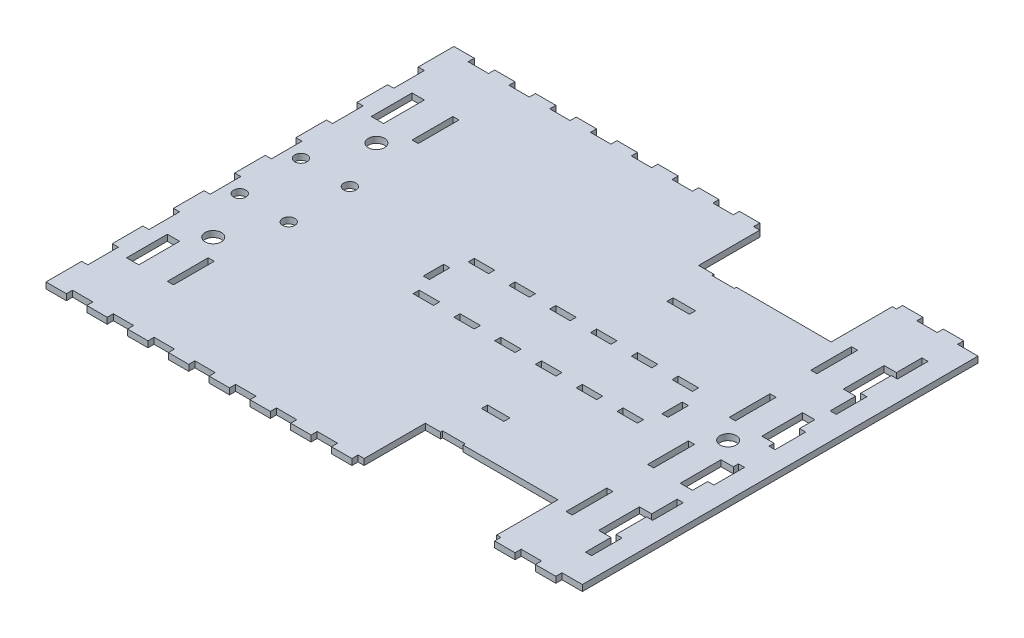
SolidWorks part; units mm, degrees
ref_plane "Front Plane" through (0, 0, 0) normal (0, 0, 1) x (1, 0, 0)
ref_plane "Top Plane" through (0, 0, 0) normal (0, 1, 0) x (1, 0, 0)
ref_plane "Right Plane" through (0, 0, 0) normal (1, 0, 0) x (0, 0, -1)
sketch "Sketch3" plane through (0, 0, 0) normal (0, 1, 0) x (1, 0, 0)
  line L0 (0, 0) -> (-300, 0) construction
  line L1 (-300, -97) -> (-300, 97)
  line L2 (-290, 100) -> (-300, 100)
  line L3 (-290, 97) -> (-290, 100)
  line L4 (-280, 97) -> (-290, 97)
  line L5 (-300, 100) -> (-300, 97)
  line L6 (-270, 100) -> (-280, 100)
  line L7 (-270, 97) -> (-270, 100)
  line L8 (-260, 97) -> (-270, 97)
  line L9 (-280, 100) -> (-280, 97)
  line L10 (-250, 100) -> (-260, 100)
  line L11 (-250, 97) -> (-250, 100)
  line L12 (-240, 97) -> (-250, 97)
  line L13 (-260, 100) -> (-260, 97)
  line L14 (-150, -100) -> (-150, 100) construction
  line L15 (-230, 100) -> (-240, 100)
  line L16 (-230, 97) -> (-230, 100)
  line L17 (-220, 97) -> (-230, 97)
  line L18 (-240, 100) -> (-240, 97)
  line L19 (-210, 100) -> (-220, 100)
  line L20 (-210, 97) -> (-210, 100)
  line L21 (-200, 97) -> (-210, 97)
  line L22 (-40, 97) -> (-40, -97)
  line L23 (-50, 37.5) -> (-53, 37.5)
  line L24 (-50, 7.5) -> (-53, 7.5)
  line L25 (-50, -45.947) -> (-50, 45.947) construction
  line L26 (-247, 37.5) -> (-250, 37.5) construction
  line L27 (-247, 7.5) -> (-250, 7.5) construction
  line L28 (-247, 48.5) -> (-247, -48.5) construction
  line L29 (-247, 48.5) -> (-223, 48.5) construction
  line L30 (-223, 48.5) -> (-223, -48.5) construction
  line L31 (-210, 15) -> (-90, 15) construction
  line L32 (-90, 15) -> (-90, 5) construction
  line L33 (-50, 7.5) -> (-50, 22.5)
  line L34 (-220, 100) -> (-220, 97)
  line L35 (-190, 100) -> (-200, 100)
  line L36 (-190, 97) -> (-190, 100)
  line L37 (-180, 97) -> (-190, 97)
  line L38 (-200, 100) -> (-200, 97)
  line L39 (-170, 100) -> (-180, 100)
  line L40 (-170, 97) -> (-170, 100)
  line L41 (-160, 97) -> (-170, 97)
  line L42 (-180, 100) -> (-180, 97)
  line L43 (-150, 100) -> (-160, 100)
  line L44 (-150, 97) -> (-150, 100)
  line L45 (-140, 97) -> (-150, 97)
  line L46 (-160, 100) -> (-160, 97)
  line L47 (-130, 100) -> (-140, 100)
  line L48 (-130, 97) -> (-130, 100)
  line L49 (-120, 97) -> (-130, 97)
  line L50 (-140, 100) -> (-140, 97)
  line L51 (-110, 100) -> (-120, 100)
  line L52 (-110, 97) -> (-110, 100)
  line L53 (-100, 97) -> (-110, 97)
  line L54 (-120, 100) -> (-120, 97)
  line L55 (-90, 100) -> (-100, 100)
  line L56 (-90, 97) -> (-90, 100)
  line L57 (-80, 97) -> (-90, 97)
  line L58 (-100, 100) -> (-100, 97)
  line L59 (-70, 100) -> (-80, 100)
  line L60 (-70, 97) -> (-70, 100)
  line L61 (-60, 97) -> (-70, 97)
  line L62 (-80, 100) -> (-80, 97)
  line L63 (-50, 100) -> (-60, 100)
  line L64 (-50, 97) -> (-50, 100)
  line L65 (-40, 97) -> (-50, 97)
  line L66 (-60, 100) -> (-60, 97)
  line L67 (-50, 22.5) -> (-53, 22.5)
  line L68 (-210, -15) -> (-90, -15) construction
  line L69 (-53, 7.5) -> (-53, 22.5)
  line L70 (-50, 37.5) -> (-50, 52.5)
  line L71 (-50, 52.5) -> (-53, 52.5)
  line L72 (-53, 37.5) -> (-53, 52.5)
  line L73 (-50, 67.5) -> (-53, 67.5)
  line L74 (-50, 67.5) -> (-50, 82.5)
  line L75 (-50, 82.5) -> (-53, 82.5)
  line L76 (-60, -100) -> (-60, -97)
  line L77 (-40, -97) -> (-50, -97)
  line L78 (-50, -97) -> (-50, -100)
  line L79 (-50, -100) -> (-60, -100)
  line L80 (-80, -100) -> (-80, -97)
  line L81 (-60, -97) -> (-70, -97)
  line L82 (-70, -97) -> (-70, -100)
  line L83 (-70, -100) -> (-80, -100)
  line L84 (-100, -100) -> (-100, -97)
  line L85 (-80, -97) -> (-90, -97)
  line L86 (-90, -97) -> (-90, -100)
  line L87 (-90, -100) -> (-100, -100)
  line L88 (-120, -100) -> (-120, -97)
  line L89 (-100, -97) -> (-110, -97)
  line L90 (-110, -97) -> (-110, -100)
  line L91 (-110, -100) -> (-120, -100)
  line L92 (-140, -100) -> (-140, -97)
  line L93 (-120, -97) -> (-130, -97)
  line L94 (-130, -97) -> (-130, -100)
  line L95 (-130, -100) -> (-140, -100)
  line L96 (-160, -100) -> (-160, -97)
  line L97 (-140, -97) -> (-150, -97)
  line L98 (-150, -97) -> (-150, -100)
  line L99 (-150, -100) -> (-160, -100)
  line L100 (-180, -100) -> (-180, -97)
  line L101 (-160, -97) -> (-170, -97)
  line L102 (-170, -97) -> (-170, -100)
  line L103 (-170, -100) -> (-180, -100)
  line L104 (-200, -100) -> (-200, -97)
  line L105 (-180, -97) -> (-190, -97)
  line L106 (-190, -97) -> (-190, -100)
  line L107 (-190, -100) -> (-200, -100)
  line L108 (-247, -48.5) -> (-223, -48.5) construction
  line L109 (-247, 7.5) -> (-247, 22.5) construction
  line L110 (-220, -100) -> (-220, -97)
  line L111 (-53, 67.5) -> (-53, 82.5)
  line L112 (-53, -67.5) -> (-53, -82.5)
  line L113 (-50, -82.5) -> (-53, -82.5)
  line L114 (-200, -97) -> (-210, -97)
  line L115 (-210, -97) -> (-210, -100)
  line L116 (-210, -100) -> (-220, -100)
  line L117 (-240, -100) -> (-240, -97)
  line L118 (-220, -97) -> (-230, -97)
  line L119 (-230, -97) -> (-230, -100)
  line L120 (-230, -100) -> (-240, -100)
  line L121 (-50, -67.5) -> (-50, -82.5)
  line L122 (-260, -100) -> (-260, -97)
  line L123 (-240, -97) -> (-250, -97)
  line L124 (-250, -97) -> (-250, -100)
  line L125 (-250, -100) -> (-260, -100)
  line L126 (-280, -100) -> (-280, -97)
  line L127 (-260, -97) -> (-270, -97)
  line L128 (-270, -97) -> (-270, -100)
  line L129 (-270, -100) -> (-280, -100)
  line L130 (-300, -100) -> (-300, -97)
  line L131 (-210, 15) -> (-210, -15) construction
  line L132 (-115, 15) -> (-125, 15)
  line L133 (-90, 5) -> (-93, 5)
  line L134 (-90, 5) -> (-90, -5)
  line L135 (-90, -5) -> (-93, -5)
  line L136 (-93, 5) -> (-93, -5)
  line L137 (-95, 15) -> (-105, 15)
  line L138 (-95, 15) -> (-95, 12)
  line L139 (-95, 12) -> (-105, 12)
  line L140 (-105, 15) -> (-105, 12)
  line L141 (-115, 12) -> (-125, 12)
  line L142 (-125, 15) -> (-125, 12)
  line L143 (-135, 15) -> (-145, 15)
  line L144 (-135, 12) -> (-145, 12)
  line L145 (-145, 15) -> (-145, 12)
  line L146 (-155, 15) -> (-165, 15)
  line L147 (-155, 12) -> (-165, 12)
  line L148 (-165, 15) -> (-165, 12)
  line L149 (-175, 15) -> (-185, 15)
  line L150 (-175, 12) -> (-185, 12)
  line L151 (-185, 15) -> (-185, 12)
  line L152 (-195, 15) -> (-205, 15)
  line L153 (-195, 12) -> (-205, 12)
  line L154 (-205, 15) -> (-205, 12)
  line L155 (-195, 12) -> (-195, 15)
  line L156 (-175, 12) -> (-175, 15)
  line L157 (-155, 12) -> (-155, 15)
  line L158 (-135, 12) -> (-135, 15)
  line L159 (-115, 12) -> (-115, 15)
  line L160 (-207, 5) -> (-207, -5)
  line L161 (-210, -5) -> (-207, -5)
  line L162 (-210, 5) -> (-210, -5)
  line L163 (-210, 5) -> (-207, 5)
  line L164 (-115, -12) -> (-115, -15)
  line L165 (-135, -12) -> (-135, -15)
  line L166 (-155, -12) -> (-155, -15)
  line L167 (-175, -12) -> (-175, -15)
  line L168 (-195, -12) -> (-195, -15)
  line L169 (-205, -15) -> (-205, -12)
  line L170 (-195, -12) -> (-205, -12)
  line L171 (-195, -15) -> (-205, -15)
  line L172 (-185, -15) -> (-185, -12)
  line L173 (-175, -12) -> (-185, -12)
  line L174 (-175, -15) -> (-185, -15)
  line L175 (-165, -15) -> (-165, -12)
  line L176 (-155, -12) -> (-165, -12)
  line L177 (-155, -15) -> (-165, -15)
  line L178 (-145, -15) -> (-145, -12)
  line L179 (-135, -12) -> (-145, -12)
  line L180 (-135, -15) -> (-145, -15)
  line L181 (-125, -15) -> (-125, -12)
  line L182 (-115, -12) -> (-125, -12)
  line L183 (-105, -15) -> (-105, -12)
  line L184 (-95, -12) -> (-105, -12)
  line L185 (-95, -15) -> (-95, -12)
  line L186 (-95, -15) -> (-105, -15)
  line L187 (-115, -15) -> (-125, -15)
  line L188 (-247, 22.5) -> (-250, 22.5) construction
  line L189 (-250, 7.5) -> (-250, 22.5) construction
  line L190 (-247, 37.5) -> (-247, 52.5) construction
  line L191 (-247, 52.5) -> (-250, 52.5) construction
  line L192 (-250, 37.5) -> (-250, 52.5) construction
  line L193 (-247, 67.5) -> (-250, 67.5) construction
  line L194 (-247, 67.5) -> (-247, 82.5) construction
  line L195 (-247, 82.5) -> (-250, 82.5) construction
  line L196 (-250, 67.5) -> (-250, 82.5) construction
  line L197 (-250, -67.5) -> (-250, -82.5) construction
  line L198 (-247, -82.5) -> (-250, -82.5) construction
  line L199 (-247, -67.5) -> (-247, -82.5) construction
  line L200 (-247, -67.5) -> (-250, -67.5) construction
  line L201 (-250, -37.5) -> (-250, -52.5) construction
  line L202 (-247, -52.5) -> (-250, -52.5) construction
  line L203 (-247, -37.5) -> (-247, -52.5) construction
  line L204 (-250, -7.5) -> (-250, -22.5) construction
  line L205 (-247, -22.5) -> (-250, -22.5) construction
  line L206 (-247, -7.5) -> (-247, -22.5) construction
  line L207 (-247, -7.5) -> (-250, -7.5) construction
  line L208 (-247, -37.5) -> (-250, -37.5) construction
  line L209 (-50, -67.5) -> (-53, -67.5)
  line L210 (-53, -37.5) -> (-53, -52.5)
  line L211 (-50, -52.5) -> (-53, -52.5)
  line L212 (-50, -37.5) -> (-50, -52.5)
  line L213 (-53, -7.5) -> (-53, -22.5)
  line L214 (-50, -22.5) -> (-53, -22.5)
  line L215 (-50, -7.5) -> (-50, -22.5)
  line L216 (-50, -7.5) -> (-53, -7.5)
  line L217 (-50, -37.5) -> (-53, -37.5)
  line L231 (-280, -97) -> (-290, -97)
  line L232 (-290, -97) -> (-290, -100)
  line L233 (-290, -100) -> (-300, -100)
  circle A0 centre (-290, 15) radius 3
  circle A1 centre (-266, 15) radius 3
  circle A2 centre (-266, -15) radius 3
  circle A3 centre (-290, -15) radius 3
  point P31 (-250, 36)
  point P80 (-91.5, 0)
  point P82 (-150, 0)
  point P126 (-223, 0)
  point P128 (-250, 18)
  point P129 (-50, 0)
  point P150 (-150, -15)
  point P151 (-150, 15)
  point P183 (-208.5, 0)
  point P212 (-223, 18)
  point P218 (-223, 36)
  dimension "D17" = 6
  dimension "D18" = 6
  dimension "D1" = 300
  dimension "D4" = 7.5
  dimension "D5" = 100
  dimension "D6" = 97
  dimension "D7" = 15
  dimension "D8" = 97
  dimension "D9" = 3
  dimension "D10" = 3
  dimension "D11" = 48.5
  dimension "D12" = 24
  dimension "D13" = 60
  dimension "D14" = 15
  dimension "D15" = 24
  dimension "D16" = 15
  dimension "D19" = 194
  dimension "D20" = 10
  dimension "D21" = 3
  dimension "D22" = 7.5
  dimension "D23" = 15
  dimension "D24" = 3
  dimension "D25" = 3
  dimension "D29" = 10
  dimension "D30" = 3
  dimension "D31" = 10
  dimension "D32" = 3
  dimension "D33" = 10
  dimension "D34" = 5
  dimension "D35" = 6
  dimension "D36" = 3
extrude "Boss-Extrude1" add sketch "Sketch3" along normal blind 3 contours L1 L116 L115 L107 L106 L83 L82 L79 L95 L98 L99 L91 L90 L86 region at (-170.6363, 0, 0)
sketch "Sketch5" plane through (0, 3, 0) normal (0, 1, 0) x (1, 0, 0)
  line L0 (-82, 0) -> (-82, 67) construction
  line L2 (-82, 67) -> (-128.5, 67)
  line L3 (-82, 67) -> (-82, 97)
  line L4 (-82, 97) -> (-147, 97)
  line L5 (-147, 67) -> (-147, 97)
  line L7 (-110, 100) -> (-120, 100) construction
  line L8 (-82, 0) -> (-300, 0) construction
  line L9 (-300, 100) -> (-300, -100) construction
  line L10 (-147, -67) -> (-147, -97)
  line L11 (-82, -97) -> (-147, -97)
  line L12 (-82, -67) -> (-82, -97)
  line L13 (-82, -67) -> (-128.5, -67)
  line L14 (-114.5, -67) -> (-114.5, -47) construction
  line L15 (-114.5, -47) -> (-128.5, -47) construction
  line L16 (-128.5, -47) -> (-128.5, -44)
  line L17 (-128.5, -44) -> (-139.5, -44)
  line L18 (-139.5, -44) -> (-139.5, -47)
  line L19 (-139.5, -47) -> (-128.5, -47)
  line L20 (-128.5, -67) -> (-128.5, -66)
  line L21 (-128.5, -66) -> (-139.5, -66)
  line L22 (-139.5, -66) -> (-139.5, -67)
  line L23 (-139.5, -67) -> (-147, -67)
  line L24 (-114.5, 47) -> (-128.5, 47) construction
  line L25 (-114.5, 67) -> (-114.5, 47) construction
  line L26 (-139.5, 66) -> (-139.5, 67)
  line L27 (-128.5, 66) -> (-139.5, 66)
  line L28 (-128.5, 67) -> (-128.5, 66)
  line L29 (-139.5, 47) -> (-128.5, 47)
  line L30 (-139.5, 44) -> (-139.5, 47)
  line L31 (-128.5, 44) -> (-139.5, 44)
  line L32 (-128.5, 47) -> (-128.5, 44)
  line L33 (-139.5, 67) -> (-147, 67)
  dimension "D2" = 30
  dimension "D3" = 3
  dimension "D5" = 14
  dimension "D6" = 3
  dimension "D7" = 11
  dimension "D8" = 20
  dimension "D9" = 1
extrude "Cut-Extrude2" cut sketch "Sketch5" against normal blind 10 contours L5 L2 L3 L4 | L12 L13 L10 L11 | L31 L30 L29 L32 | L17 L18 L19 L16 region at (-114.6094, 3, -81.9131) region at (-114.6094, 3, 81.9131) body kept at (-300, 0, -100)
sketch "Croquis1" plane through (0, 3, 0) normal (0, 1, 0) x (1, 0, 0)
  line L0 (-300, -67.5) -> (-300, -82.5)
  line L25 (-300, 100) -> (-300, -100) construction
  line L26 (-300, 37.5) -> (-300, 52.5)
  line L27 (-297, 37.5) -> (-300, 37.5)
  line L28 (-297, 7.5) -> (-300, 7.5)
  line L29 (-300, -7.5) -> (-297, -7.5)
  line L30 (-297, -22.5) -> (-300, -22.5)
  line L31 (-297, -7.5) -> (-297, -22.5)
  line L32 (-297, 82.5) -> (-297, 67.5)
  line L33 (-300, -22.5) -> (-300, -7.5)
  line L34 (-297, -37.5) -> (-297, -52.5)
  line L35 (-297, 67.5) -> (-300, 67.5)
  line L36 (-300, 67.5) -> (-300, 82.5)
  line L37 (-297, 52.5) -> (-297, 37.5)
  line L38 (-300, 22.5) -> (-297, 22.5)
  line L39 (-300, -37.5) -> (-297, -37.5)
  line L40 (-297, -52.5) -> (-300, -52.5)
  line L41 (-300, 52.5) -> (-297, 52.5)
  line L42 (-300, -52.5) -> (-300, -37.5)
  line L43 (-300, 82.5) -> (-297, 82.5)
  line L44 (-297, 22.5) -> (-297, 7.5)
  line L45 (-300, 7.5) -> (-300, 22.5)
  line L46 (-300, -67.5) -> (-297, -67.5)
  line L47 (-297, -67.5) -> (-297, -82.5)
  line L48 (-297, -82.5) -> (-300, -82.5)
  dimension "D1" = 15
  dimension "D2" = 15
extrude "Cortar-Extruir1" cut sketch "Croquis1" against normal blind 10
sketch "Croquis2" plane through (0, 3, 0) normal (0, 1, 0) x (1, 0, 0)
  line L0 (-40, 0) -> (-53, 0) construction
  line L1 (-40, 97) -> (-40, -97) construction
  line L2 (-53, 10) -> (-53, -10) construction
  line L3 (-53, -7.5) -> (-53, -22.5) construction
  line L4 (-53, -10) -> (-59, -10)
  line L5 (-59, -10) -> (-59, -30)
  line L6 (-59, -30) -> (-53, -30)
  line L7 (-53, -30) -> (-53, -10)
  line L8 (-53, -30) -> (-53, -50) construction
  line L9 (-53, -37.5) -> (-53, -52.5) construction
  line L10 (-53, -50) -> (-59, -50)
  line L11 (-59, -50) -> (-59, -70)
  line L12 (-59, -70) -> (-53, -70)
  line L13 (-53, -67.5) -> (-53, -82.5) construction
  line L14 (-53, -70) -> (-53, -50)
  line L15 (-53, 30) -> (-53, 50) construction
  line L16 (-53, 70) -> (-53, 50)
  line L17 (-59, 70) -> (-53, 70)
  line L18 (-59, 50) -> (-59, 70)
  line L19 (-53, 50) -> (-59, 50)
  line L20 (-53, 30) -> (-53, 10)
  line L21 (-59, 30) -> (-53, 30)
  line L22 (-59, 10) -> (-59, 30)
  line L23 (-53, 10) -> (-59, 10)
  line L24 (-59, 70) -> (-72, 70) construction
  line L25 (-72, 70) -> (-75, 70)
  line L26 (-72, 70) -> (-72, 50)
  line L27 (-72, 50) -> (-75, 50)
  line L28 (-75, 50) -> (-75, 70)
  line L29 (-72, 30) -> (-75, 30)
  line L30 (-75, 30) -> (-75, 10)
  line L31 (-75, 10) -> (-72, 10)
  line L32 (-72, 10) -> (-72, 30)
  line L33 (-72, -10) -> (-75, -10)
  line L34 (-75, -10) -> (-75, -30)
  line L35 (-75, -30) -> (-72, -30)
  line L36 (-72, -30) -> (-72, -10)
  line L37 (-72, -50) -> (-75, -50)
  line L38 (-75, -50) -> (-75, -70)
  line L39 (-75, -70) -> (-72, -70)
  line L40 (-72, -70) -> (-72, -50)
  line L45 (-290.5, 30) -> (-290.5, 50) construction
  line L46 (-290.5, -30) -> (-290.5, -50) construction
  line L49 (-270.5, -70) -> (-270.5, -50)
  line L50 (-267.5, -70) -> (-270.5, -70)
  line L51 (-267.5, -50) -> (-267.5, -70)
  line L52 (-270.5, -50) -> (-267.5, -50)
  line L61 (-267.5, 50) -> (-267.5, 70)
  line L62 (-270.5, 50) -> (-267.5, 50)
  line L63 (-270.5, 70) -> (-270.5, 50)
  line L64 (-270.5, 70) -> (-267.5, 70)
  line L69 (-290.5, 50) -> (-284.5, 50)
  line L70 (-284.5, 50) -> (-284.5, 70)
  line L71 (-284.5, 70) -> (-290.5, 70)
  line L72 (-290.5, 70) -> (-290.5, 50)
  line L73 (-290.5, -70) -> (-290.5, -50)
  line L74 (-284.5, -70) -> (-290.5, -70)
  line L75 (-284.5, -50) -> (-284.5, -70)
  line L76 (-290.5, -50) -> (-284.5, -50)
  circle A0 centre (-65.5, 0) radius 4
  circle A3 centre (-278, -40) radius 4
  circle A4 centre (-278, 40) radius 4
  dimension "D8" = 8
  dimension "D11" = 8
  dimension "D12" = 8
  dimension "D1" = 10
  dimension "D2" = 6
  dimension "D3" = 20
  dimension "D4" = 20
  dimension "D5" = 13
  dimension "D6" = 3
  dimension "D7" = 20
  dimension "D9" = 14
extrude "Cortar-Extruir2" cut sketch "Croquis2" against normal blind 10
